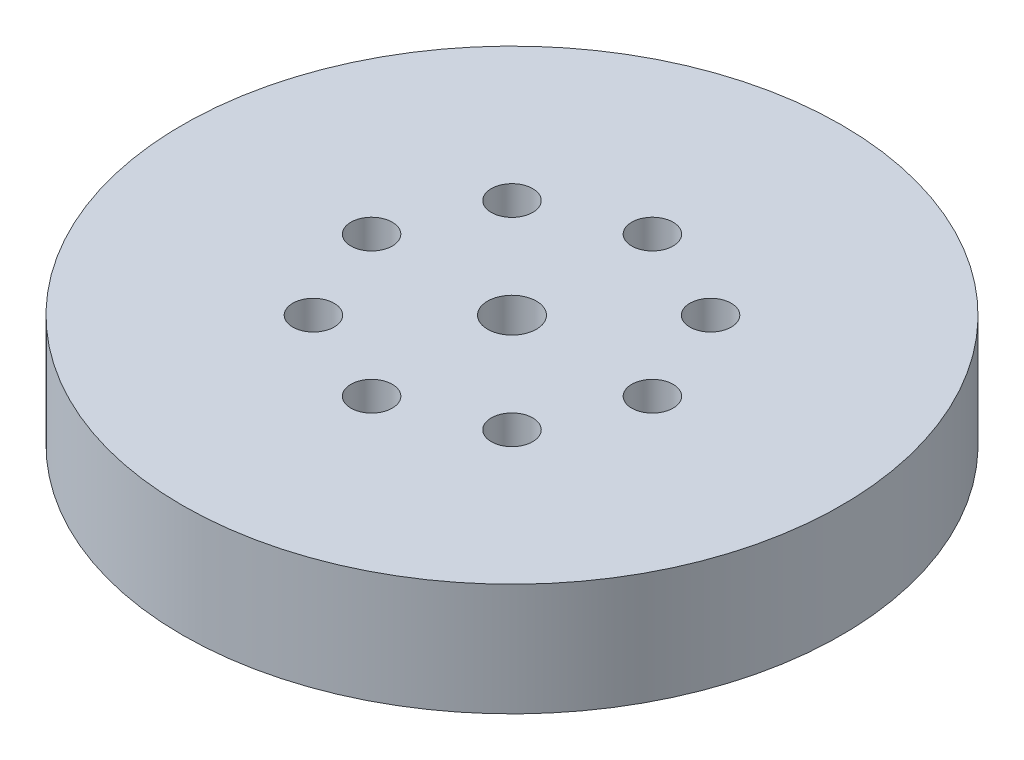
SolidWorks part; units mm, degrees
ref_plane "Front Plane" through (0, 0, 0) normal (0, 0, 1) x (1, 0, 0)
ref_plane "Top Plane" through (0, 0, 0) normal (0, 1, 0) x (1, 0, 0)
ref_plane "Right Plane" through (0, 0, 0) normal (1, 0, 0) x (0, 0, -1)
sketch "Sketch1" plane through (0, 0, 0) normal (0, 1, 0) x (1, 0, 0)
  circle A0 centre (0, 0) radius 67.5
  dimension "FLANGE_OD" = 135
extrude "Boss-Extrude1" add sketch "Sketch1" along normal blind 23
sketch "Sketch2" plane through (0, 0, 0) normal (0, 1, 0) x (1, 0, 0)
  circle A0 centre (0, 0) radius 5
  dimension "BORE_D" = 10
extrude "Cut-Extrude1" cut sketch "Sketch2" along normal through all
sketch "Sketch3" plane through (0, 23, 0) normal (0, 1, 0) x (1, 0, 0)
  circle A0 centre (0, 0) radius 28.7572 construction
  circle A1 centre (-28.7572, 0) radius 4.2391
  dimension "BOLT_D" = 8.4782
  dimension "BOLT_PCD" = 57.5143
extrude "Cut-Extrude2" cut sketch "Sketch3" against normal blind 21.7365
pattern_circular "CirPattern1" count 8 over 360 about axis through (0, 0, 0) along (0, 1, 0) of "Cut-Extrude2"
